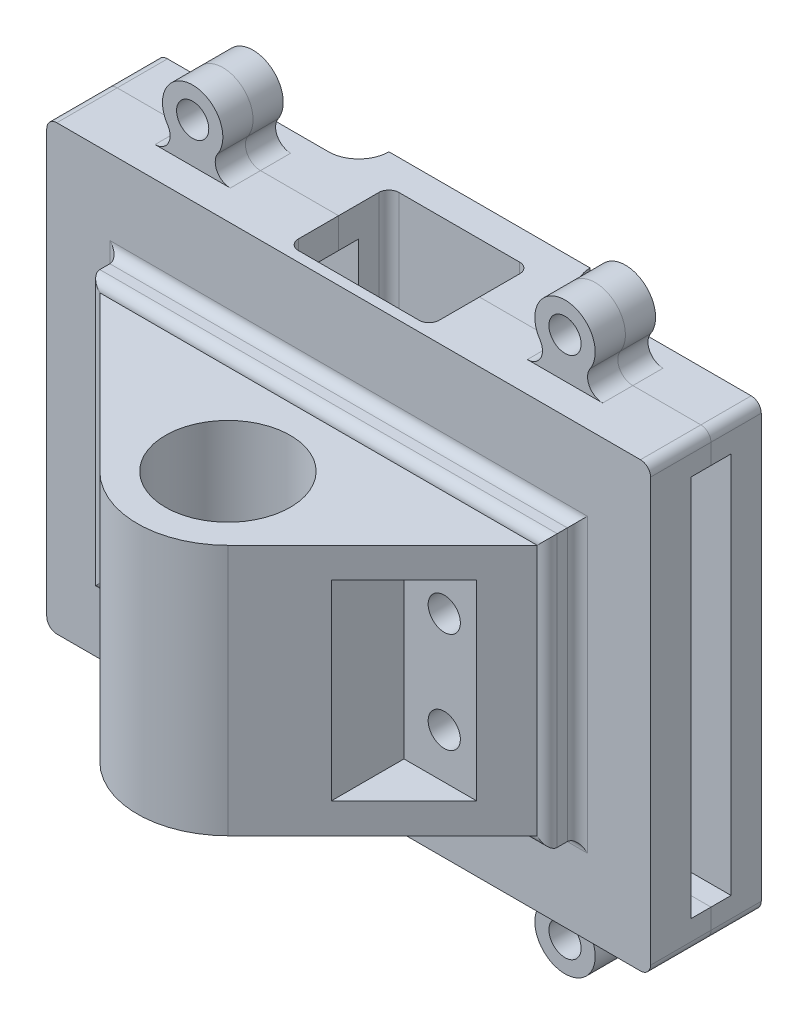
SolidWorks part; units mm, degrees
ref_plane "前视基准面" through (0, 0, 0) normal (0, 0, 1) x (1, 0, 0)
ref_plane "上视基准面" through (0, 0, 0) normal (0, 1, 0) x (1, 0, 0)
ref_plane "右视基准面" through (0, 0, 0) normal (1, 0, 0) x (0, 0, -1)
sketch "草图1" plane through (0, 0, 0) normal (0, 1, 0) x (1, 0, 0)
  line L0 (0, 11.3377) -> (0, -10.6482) construction
  line L1 (-6.364, -6.364) -> (-21.7279, 9)
  line L2 (-21.7279, 9) -> (21.7279, 9)
  line L3 (6.364, -6.364) -> (21.7279, 9)
  circle A0 centre (0, 0) radius 9
  point P12 (0, 9)
  dimension "D1" = 18
  dimension "D2" = 45
extrude "凸台-拉伸1" add sketch "草图1" along normal blind 25 contours A0 L2 L1 | A0 L3 L2 | A0 L0 | L0 A0 region at (3.8197, 0, 0) region at (-12.0738, 0, -5.0011) region at (12.0738, 0, -5.0011) region at (-3.8197, 0, 0)
sketch "草图2" plane through (0, 25, 0) normal (0, 1, 0) x (1, 0, 0)
  circle A0 centre (0, 0) radius 6.2
  dimension "D1" = 12.4
extrude "切除-拉伸1" cut sketch "草图2" against normal offset from surface (20 mm away) 5 up to face at (0, 0, -0.659)
ref_plane "基准面1" through (0, 0, 9) normal (0, 0, 1) x (1, 0, 0)
sketch "草图3" plane through (0, 0, 9) normal (0, 0, 1) x (1, 0, 0)
  line L0 (0, 29.4282) -> (0, -7.375) construction
  line L1 (-21.7279, 12.5) -> (21.7279, 12.5) construction
  line L2 (-21.7279, 25) -> (-21.7279, 0) construction
  line L3 (21.7279, 25) -> (21.7279, 0) construction
  line L4 (29.7362, 22) -> (11.5, 22)
  line L5 (-29.7362, 3) -> (-11.5, 3)
  line L6 (-29.7362, 3) -> (-29.7362, 22)
  line L7 (-29.7362, 22) -> (-11.5, 22)
  line L8 (-11.5, 3) -> (-11.5, 22)
  line L9 (-29.7362, 3) -> (-11.5, 22) construction
  line L10 (-29.7362, 22) -> (-11.5, 3) construction
  line L11 (11.5, 3) -> (11.5, 22)
  line L12 (29.7362, 3) -> (11.5, 3)
  line L13 (29.7362, 3) -> (29.7362, 22)
  line L14 (-6.364, 25) -> (-21.7279, 25) construction
  point P9 (-20.6181, 12.5)
  dimension "D1" = 23
  dimension "D2" = 3
extrude "切除-拉伸2" cut sketch "草图3" against normal offset from surface (15 mm away) 3 up to face at (0, 12.5, -9)
sketch "草图5" plane through (0, 0, -9) normal (0, 0, -1) x (-1, 0, 0)
  line L0 (0, 25) -> (0, 0) construction
  line L1 (21.7279, 25) -> (-21.7279, 25) construction
  line L3 (-30, -9.5) -> (30, -9.5)
  line L4 (-30, -9.5) -> (-30, 34.5)
  line L5 (-30, 34.5) -> (30, 34.5)
  line L6 (30, -9.5) -> (30, 34.5)
  line L7 (-30, -9.5) -> (30, 34.5) construction
  line L8 (-30, 34.5) -> (30, -9.5) construction
  point P5 (0, 12.5)
  dimension "D1" = 60
  dimension "D2" = 44
extrude "凸台-拉伸2" add sketch "草图5" along normal blind 14
sketch "草图6" plane through (-30, 0, 0) normal (-1, 0, 0) x (0, 0, 1)
  line L0 (-9, -9.5) -> (-9, 34.5) construction
  line L3 (-23, 12.5) -> (-9, 12.5) construction
  line L4 (-23, -9.5) -> (-23, 34.5) construction
  line L5 (-9, 25) -> (-9, 0) construction
  line L7 (-20, -6.5) -> (-16, -6.5)
  line L8 (-20, -6.5) -> (-20, 31.5)
  line L9 (-20, 31.5) -> (-16, 31.5)
  line L10 (-16, -6.5) -> (-16, 31.5)
  line L11 (-20, -6.5) -> (-16, 31.5) construction
  line L12 (-20, 31.5) -> (-16, -6.5) construction
  point P12 (-18, 12.5)
  dimension "D1" = 4
  dimension "D2" = 38
  dimension "D3" = 7
extrude "切除-拉伸4" cut sketch "草图6" against normal through all
sketch "草图7" plane through (0, 0, -23) normal (0, 0, -1) x (-1, 0, 0)
  line L0 (0, 34.5) -> (0, -9.5) construction
  line L1 (30, 34.5) -> (-30, 34.5) construction
  line L2 (-30, -9.5) -> (30, -9.5) construction
  line L4 (-7, -9.5) -> (7, -9.5)
  line L5 (-7, -9.5) -> (-7, 34.5)
  line L6 (-7, 34.5) -> (7, 34.5)
  line L7 (7, -9.5) -> (7, 34.5)
  line L8 (-7, -9.5) -> (7, 34.5) construction
  line L9 (-7, 34.5) -> (7, -9.5) construction
  point P7 (0, 12.5)
  dimension "D1" = 14
extrude "切除-拉伸5" cut sketch "草图7" against normal blind 10
ref_plane "基准面2" through (0, 0, -18) normal (0, 0, -1) x (-1, 0, 0)
sketch "草图9" plane through (0, 0, -18) normal (0, 0, -1) x (-1, 0, 0)
  line L0 (-18.5, -9.5) -> (-18.5, 48.9996) construction
  line L1 (0, -16.6663) -> (0, 48.9996) construction
  line L2 (-30, -9.5) -> (-7, -9.5) construction
  line L3 (30, 12.5) -> (-27.4636, 12.5) construction
  line L4 (30, -9.5) -> (30, 34.5) construction
  line L5 (-22.2417, 34.5) -> (-14.7583, 34.5)
  line L6 (22.2417, 34.5) -> (14.7583, 34.5)
  line L7 (-22.2417, -9.5) -> (-14.7583, -9.5)
  line L8 (-7, 34.5) -> (-30, 34.5) construction
  line L9 (22.2417, -9.5) -> (14.7583, -9.5)
  circle A0 centre (-18.5, 38.5) radius 1.6
  circle A1 centre (18.5, 38.5) radius 1.6
  circle A2 centre (18.5, -13.5) radius 1.6
  circle A3 centre (-18.5, -13.5) radius 1.6
  arc A4 (-16.0056, 36.8333) -> (-20.9944, 36.8333) centre (-18.5, 38.5) ccw
  arc A5 (16.0056, 36.8333) -> (20.9944, 36.8333) centre (18.5, 38.5) cw
  arc A6 (16.0056, -11.8333) -> (20.9944, -11.8333) centre (18.5, -13.5) ccw
  arc A7 (-16.0056, -11.8333) -> (-20.9944, -11.8333) centre (-18.5, -13.5) cw
  arc A8 (-22.2417, 34.5) -> (-20.9944, 36.8333) centre (-22.2417, 36) ccw
  arc A9 (-14.7583, 34.5) -> (-16.0056, 36.8333) centre (-14.7583, 36) cw
  arc A10 (14.7583, 34.5) -> (16.0056, 36.8333) centre (14.7583, 36) ccw
  arc A11 (22.2417, 34.5) -> (20.9944, 36.8333) centre (22.2417, 36) cw
  arc A12 (-14.7583, -9.5) -> (-16.0056, -11.8333) centre (-14.7583, -11) ccw
  arc A13 (-22.2417, -9.5) -> (-20.9944, -11.8333) centre (-22.2417, -11) cw
  arc A14 (22.2417, -9.5) -> (20.9944, -11.8333) centre (22.2417, -11) ccw
  arc A15 (14.7583, -9.5) -> (16.0056, -11.8333) centre (14.7583, -11) cw
  dimension "D1" = 3.2
  dimension "D2" = 6
  dimension "D4" = 3
  dimension "D3" = 4
extrude "凸台-拉伸3" add sketch "草图9" along normal mid plane 6
sketch "草图10" plane through (0, 0, -23) normal (0, 0, -1) x (-1, 0, 0)
  line L0 (30, 12.5) -> (-30, 12.5) construction
  line L1 (30, -9.5) -> (30, 34.5) construction
  line L2 (-30, 34.5) -> (-30, -9.5) construction
  line L3 (0, 34.5) -> (0, -9.5) construction
  line L4 (7, 34.5) -> (-7, 34.5) construction
  line L5 (-7, -9.5) -> (7, -9.5) construction
  line L6 (30, 34.5) -> (7, 34.5) construction
  line L7 (-10, -9.5) -> (10, -9.5)
  line L8 (-10, -9.5) -> (-10, 34.5)
  line L9 (-10, 34.5) -> (10, 34.5)
  line L10 (10, -9.5) -> (10, 34.5)
  line L11 (-10, -9.5) -> (10, 34.5) construction
  line L12 (-10, 34.5) -> (10, -9.5) construction
  line L13 (7, -9.5) -> (7, 34.5) construction
  point P12 (0, 12.5)
  dimension "D1" = 3
extrude "凸台-拉伸4" add sketch "草图10" along normal blind 3
fillet "圆角1" radius 3 2 edges at (-10, 12.5, -23) (10, 12.5, -23)
fillet "圆角2" radius 1 4 edges at (7, 12.5, -13) (-7, 12.5, -13) (7, 12.5, -23) (-7, 12.5, -23)
fillet "圆角3" radius 1 4 edges at (30, -9.5, -16) (-30, -9.5, -16) (-30, 34.5, -16) (30, 34.5, -16)
split "分割1" trim tools "基准面2" bodies to split 118 resulting bodies 115 117
sketch "草图4" plane through (0, 0, -6) normal (0, 0, 1) x (1, 0, 0)
  line L0 (0, 0) -> (0, 28.6493) construction
  line L1 (30, 33.5) -> (30, -8.5) construction
  line L4 (-21.7279, 12.5) -> (30, 12.5) construction
  circle A0 centre (-15.5, 17.5) radius 1.6
  circle A1 centre (-15.5, 7.5) radius 1.6
  circle A2 centre (15.5, 7.5) radius 1.6
  circle A3 centre (15.5, 17.5) radius 1.6
  dimension "D1" = 3.2
  dimension "D2" = 10
  dimension "D3" = 31
extrude "切除-拉伸3" cut sketch "草图4" against normal up to next (10 mm away)
sketch "草图8" plane through (0, 0, -16) normal (0, 0, -1) x (-1, 0, 0)
  line L0 (0, 25) -> (0, 0) construction
  line L1 (7, 25) -> (-7, 25) construction
  line L2 (-7, 0) -> (7, 0) construction
  line L3 (-30, 12.5) -> (23.7851, 12.5) construction
  line L4 (-30, -6.5) -> (-30, 31.5) construction
  line L5 (17.1743, 10.4) -> (18.8486, 7.5)
  line L6 (18.8486, 17.5) -> (17.1743, 20.4)
  line L7 (17.1743, 20.4) -> (13.8257, 20.4)
  line L8 (13.8257, 20.4) -> (12.1514, 17.5)
  line L9 (12.1514, 17.5) -> (13.8257, 14.6)
  line L10 (13.8257, 14.6) -> (17.1743, 14.6)
  line L11 (17.1743, 14.6) -> (18.8486, 17.5)
  line L12 (13.8257, 10.4) -> (17.1743, 10.4)
  line L13 (12.1514, 7.5) -> (13.8257, 10.4)
  line L14 (13.8257, 4.6) -> (12.1514, 7.5)
  line L15 (17.1743, 4.6) -> (13.8257, 4.6)
  line L16 (18.8486, 7.5) -> (17.1743, 4.6)
  line L17 (-13.8257, 10.4) -> (-17.1743, 10.4)
  line L18 (-12.1514, 7.5) -> (-13.8257, 10.4)
  line L19 (-13.8257, 4.6) -> (-12.1514, 7.5)
  line L20 (-17.1743, 4.6) -> (-13.8257, 4.6)
  line L21 (-18.8486, 7.5) -> (-17.1743, 4.6)
  line L22 (-17.1743, 10.4) -> (-18.8486, 7.5)
  line L23 (-17.1743, 14.6) -> (-18.8486, 17.5)
  line L24 (-13.8257, 14.6) -> (-17.1743, 14.6)
  line L25 (-12.1514, 17.5) -> (-13.8257, 14.6)
  line L26 (-13.8257, 20.4) -> (-12.1514, 17.5)
  line L27 (-17.1743, 20.4) -> (-13.8257, 20.4)
  line L28 (-18.8486, 17.5) -> (-17.1743, 20.4)
  circle A0 centre (15.5, 17.5) radius 2.9 construction
  dimension "D1" = 5.8
extrude "切除-拉伸6" cut sketch "草图8" against normal blind 4
sketch "草图11" plane through (0, 0, -9) normal (0, 0, 1) x (1, 0, 0)
  line L4 (-29, -9.5) -> (29, -9.5)
  line L5 (30, -8.5) -> (30, 33.5)
  line L6 (29, 34.5) -> (-29, 34.5)
  line L7 (-30, 33.5) -> (-30, -8.5)
  line L8 (-29, -9.5) -> (29, -9.5)
  line L9 (30, -8.5) -> (30, 33.5)
  line L10 (29, 34.5) -> (-29, 34.5)
  line L11 (-30, 33.5) -> (-30, -8.5)
  line L16 (-22.7279, -1) -> (22.7279, -1)
  line L17 (22.7279, -1) -> (22.7279, 26)
  line L18 (-22.7279, 26) -> (-22.7279, -1)
  line L19 (22.7279, 26) -> (-22.7279, 26)
  line L20 (-22.7279, -1) -> (22.7279, -1)
  line L21 (22.7279, -1) -> (22.7279, 26)
  line L22 (-22.7279, 26) -> (-22.7279, -1)
  line L23 (22.7279, 26) -> (-22.7279, 26)
  arc A4 (29, -9.5) -> (30, -8.5) centre (29, -8.5) ccw
  arc A5 (30, 33.5) -> (29, 34.5) centre (29, 33.5) ccw
  arc A6 (-29, 34.5) -> (-30, 33.5) centre (-29, 33.5) ccw
  arc A7 (-30, -8.5) -> (-29, -9.5) centre (-29, -8.5) ccw
  arc A8 (29, -9.5) -> (30, -8.5) centre (29, -8.5) ccw
  arc A9 (30, 33.5) -> (29, 34.5) centre (29, 33.5) ccw
  arc A10 (-29, 34.5) -> (-30, 33.5) centre (-29, 33.5) ccw
  arc A11 (-30, -8.5) -> (-29, -9.5) centre (-29, -8.5) ccw
  dimension "D1" = 0
  dimension "D2" = 1
extrude "切除-拉伸7" cut sketch "草图11" against normal blind 3
split "分割2" bodies to split 119 resulting bodies 120 121 split by face at (0, 12.5, -9)
fillet "圆角4" radius 1 4 edges at (-22.7279, 12.5, -12) (0, -1, -12) (22.7279, 12.5, -12) (0, 26, -12)
fillet "圆角5" radius 1 4 edges at (22.7279, 12.5, -9) (0, -1, -9) (-22.7279, 12.5, -9) (0, 26, -9)
sketch "草图12" plane through (0, 25, 0) normal (0, 1, 0) x (1, 0, 0)
  circle A0 centre (0, 0) radius 6.2 construction
  circle A1 centre (0, 0) radius 6.2
  circle A2 centre (0, 0) radius 9.2
  dimension "D1" = 3
extrude "凸台-拉伸5" [suppressed] add sketch "草图12" along normal blind 4 separate body
